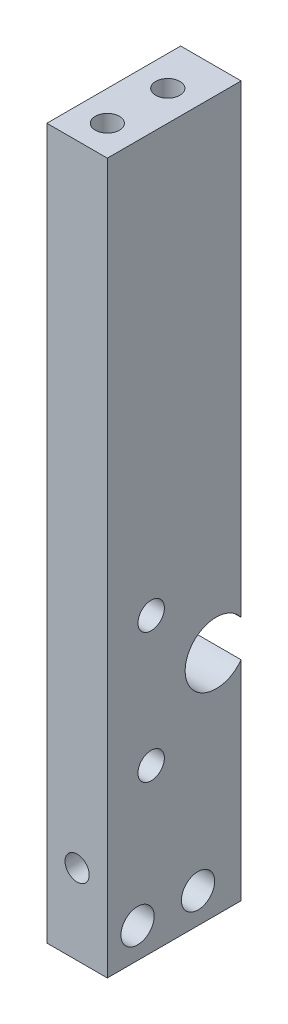
SolidWorks part; units mm, degrees
material "6061-T6 (SS)"
ref_plane "前视基准面" through (0, 0, 0) normal (0, 0, 1) x (1, 0, 0)
ref_plane "上视基准面" through (0, 0, 0) normal (0, 1, 0) x (1, 0, 0)
ref_plane "右视基准面" through (0, 0, 0) normal (1, 0, 0) x (0, 0, -1)
other "Configuration Table"
sketch "草图1" plane through (0, 0, 0) normal (0, 0, 1) x (1, 0, 0)
  line L1 (-4.3, -4.3) -> (-0.3, -4.3)
  line L2 (-4.3, -4.3) -> (-4.3, 42.68)
  line L3 (-4.3, 42.68) -> (-0.3, 42.68)
  line L4 (-0.3, -4.3) -> (-0.3, 42.68)
  dimension "D1" = 0.3
  dimension "D2" = 4.3
  dimension "D3" = 42.68
  dimension "D4" = 4.3
extrude "Main_Stock" add sketch "草图1" along normal blind 8.8519 from offset 2.2481
sketch "草图2" plane through (0, 0, 11.1) normal (0, 0, 1) x (1, 0, 0)
  circle A0 centre (-2.3, 1) radius 0.8
  dimension "D1" = 1.6
  dimension "D2" = 2.3
  dimension "D3" = 1
extrude "Frame_1xD1p6_Through" cut sketch "草图2" against normal through all
cosmetic thread "Frame_M2_Through_Cosmetic_1" parameters "D2"=2
sketch "草图3" plane through (-4.3, 0, 0) normal (-1, 0, 0) x (0, 0, 1)
  circle A0 centre (3.8995, 10.725) radius 2.05
  dimension "D1" = 4.1
  dimension "D2" = 3.8995
  dimension "D3" = 10.725
extrude "SMA_Center_D4p1" cut sketch "草图3" against normal blind 4
sketch "草图4" plane through (-4.3, 0, 0) normal (-1, 0, 0) x (0, 0, 1)
  circle A0 centre (8.1995, 6.425) radius 0.875
  circle A1 centre (8.1995, 15.025) radius 0.875
  dimension "D1" = 1.75
  dimension "D2" = 8.1995
  dimension "D3" = 6.425
  dimension "D4" = 15.025
extrude "SMA_Upper_2xD1p75_Through" cut sketch "草图4" against normal through all
cosmetic thread "SMA_Upper_Cosmetic_1" parameters "D2"=2.2
cosmetic thread "SMA_Upper_Cosmetic_2" parameters "D2"=2.2
sketch "草图5" plane through (-4.3, 0, 0) normal (-1, 0, 0) x (0, 0, 1)
  circle A0 centre (5.1, -2.3) radius 1.1
  circle A1 centre (9.1, -2.3) radius 1.1
  dimension "D1" = 2.2
  dimension "D2" = 5.1
  dimension "D3" = 9.1
  dimension "D4" = 2.3
extrude "Corner_Front_2xD2p2_Through" cut sketch "草图5" against normal through all
sketch "草图6" plane through (0, 42.68, 0) normal (0, 1, 0) x (1, 0, 0)
  circle A0 centre (-2.3, -5.1) radius 0.8
  circle A1 centre (-2.3, -9.1) radius 0.8
  dimension "D1" = 1.6
  dimension "D2" = 2.3
  dimension "D3" = 5.1
  dimension "D4" = 9.1
extrude "Corner_Rear_2xD1p6_Blind4" cut sketch "草图6" against normal blind 4
cosmetic thread "Corner_Rear_M2_Cosmetic_1" parameters "D1"=3.5, "D2"=2
cosmetic thread "Corner_Rear_M2_Cosmetic_2" parameters "D1"=3.5, "D2"=2
